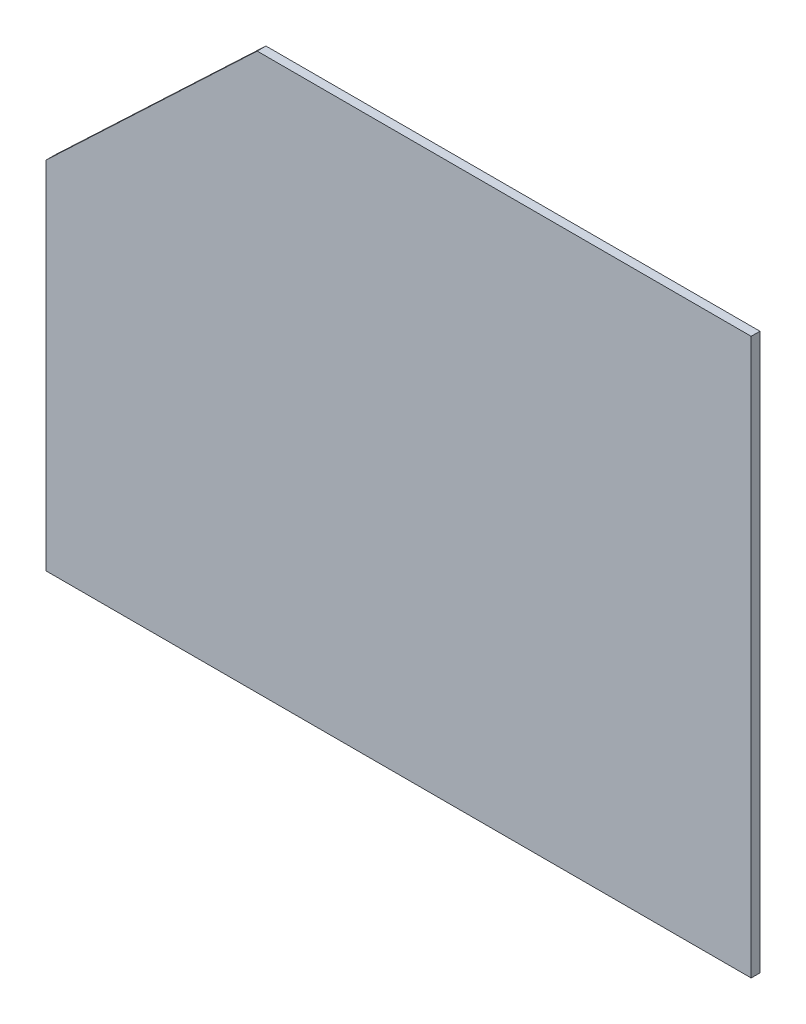
SolidWorks part; units mm, degrees
material "PVC Rigid"
ref_plane "Front Plane" through (0, 0, 0) normal (0, 0, 1) x (1, 0, 0)
ref_plane "Top Plane" through (0, 0, 0) normal (0, 1, 0) x (1, 0, 0)
ref_plane "Right Plane" through (0, 0, 0) normal (1, 0, 0) x (0, 0, -1)
sketch "Sketch1" plane through (0, 0, 0) normal (0, 0, 1) x (1, 0, 0)
  line L1 (0, 0) -> (914.4, 0)
  line L2 (0, 0) -> (0, 609.6)
  line L3 (0, 609.6) -> (914.4, 609.6)
  line L4 (914.4, 0) -> (914.4, 609.6)
  dimension "D1" = 914.4
  dimension "D2" = 609.6
extrude "Boss-Extrude1" add sketch "Sketch1" along normal blind 4.7625
sketch "Sketch2" plane through (0, 0, 4.7625) normal (0, 0, 1) x (1, 0, 0)
  line L0 (531.9566, 0) -> (531.9566, 193.0018)
  line L1 (0, 0) -> (914.4, 0) construction
  line L2 (531.9566, 193.0018) -> (646.4488, 301.4326)
  line L3 (646.4488, 301.4326) -> (914.4, 301.4326)
  line L4 (914.4, 0) -> (914.4, 609.6) construction
  line L5 (914.4, 301.4326) -> (914.4, 0)
  line L6 (914.4, 0) -> (531.9566, 0)
extrude "Cut-Extrude1" [suppressed] cut sketch "Sketch2" against normal through all
sketch "Sketch4" plane through (0, 0, 4.7625) normal (0, 0, 1) x (1, 0, 0)
  line L0 (914.4, 301.4326) -> (914.4, 609.6)
  line L1 (914.4, 609.6) -> (0, 609.6)
  line L2 (0, 609.6) -> (0, 0)
  line L3 (0, 0) -> (531.9566, 0)
  line L5 (531.9566, 193.0018) -> (531.9566, 0)
  line L6 (646.4488, 301.4326) -> (531.9566, 193.0018)
  line L7 (914.4, 301.4326) -> (646.4488, 301.4326)
  line L8 (914.4, 0) -> (914.4, 301.4326)
  line L9 (531.9566, 0) -> (914.4, 0)
  line L10 (531.9566, 193.0018) -> (531.9566, 0)
  line L11 (646.4488, 301.4326) -> (531.9566, 193.0018)
  line L12 (914.4, 301.4326) -> (646.4488, 301.4326)
  dimension "D1" = 0
extrude "Cut-Extrude2" cut sketch "Sketch4" against normal blind 4.7625
equation "\"thick\"=0.1875"
equation "\"D1@Boss-Extrude1\"=\"thick\""
